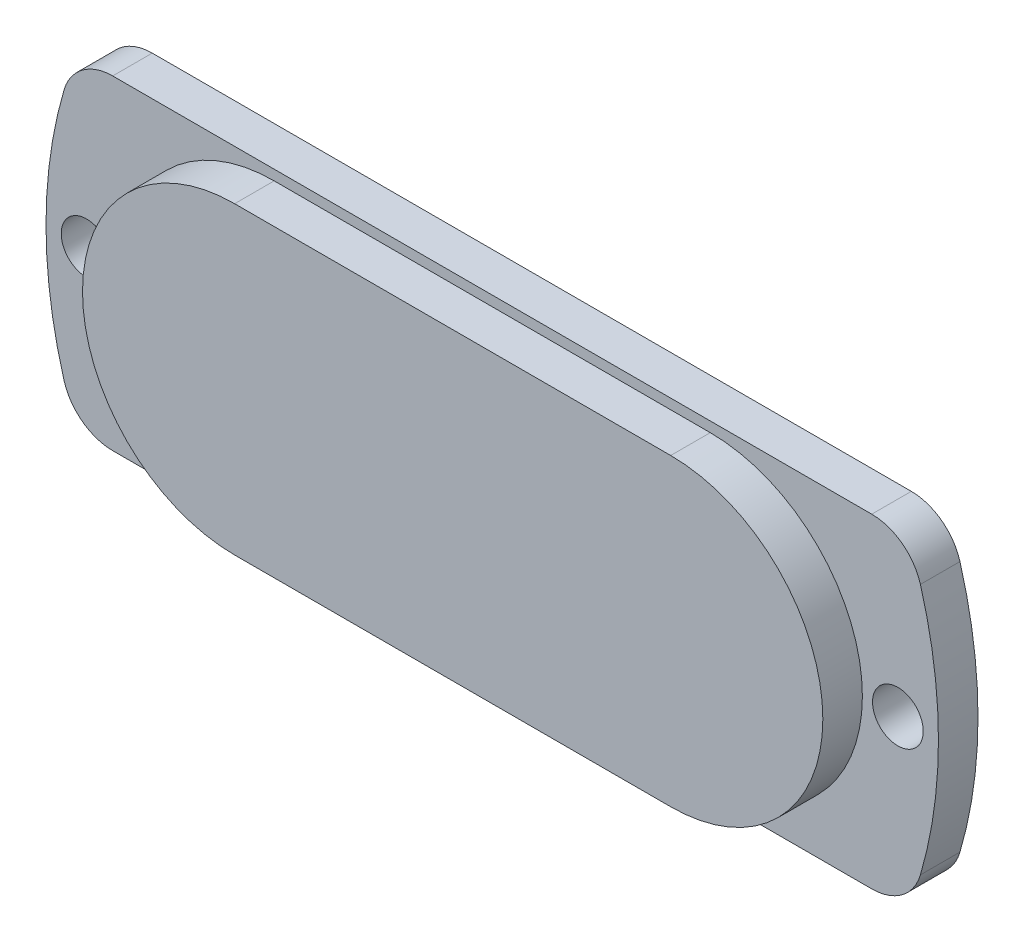
SolidWorks part; units mm, degrees
ref_plane "Front Plane" through (0, 0, 0) normal (0, 0, 1) x (1, 0, 0)
ref_plane "Top Plane" through (0, 0, 0) normal (0, 1, 0) x (1, 0, 0)
ref_plane "Right Plane" through (0, 0, 0) normal (1, 0, 0) x (0, 0, -1)
sketch "Sketch2" plane through (0, 0, 0) normal (0, 0, 1) x (1, 0, 0)
  line L0 (-55.88, 20.32) -> (55.88, 20.32)
  line L10 (-55.88, 20.32) -> (55.88, 20.32)
  line L13 (55.88, -20.32) -> (-55.88, -20.32)
  line L16 (-55.88, 20.32) -> (-55.88, -20.32)
  line L17 (-55.88, -20.32) -> (55.88, -20.32)
  line L18 (55.88, 20.32) -> (55.88, -20.32)
  line L19 (-55.88, 20.32) -> (55.88, -20.32) construction
  line L20 (-55.88, -20.32) -> (55.88, 20.32) construction
  line L21 (0, 20.32) -> (0, -20.32) construction
  circle A12 centre (50.8, 0) radius 3.175
  circle A13 centre (-50.8, 0) radius 3.175
  circle A14 centre (-50.8, 0) radius 3.175
  circle A15 centre (50.8, 0) radius 3.175
  point P3 (0, 0)
  point P4 (50.8, 0)
  point P8 (0, 0)
  dimension "D1" = 101.6
  dimension "D2" = 40.64
  dimension "D3" = 111.76
  dimension "D4" = 6.35
extrude "Boss-Extrude13" add sketch "Sketch2" along normal blind 4.953 contours L18 L0 L16 L13 A12 A13 region at (0, 0, 0)
sketch "Sketch3" plane through (0, 0, 4.953) normal (0, 0, 1) x (1, 0, 0)
  line L0 (27.305, 0) -> (-27.305, 0) construction
  line L1 (27.305, -19.05) -> (-27.305, -19.05)
  line L2 (27.305, 19.05) -> (-27.305, 19.05)
  arc A0 (27.305, -19.05) -> (27.305, 19.05) centre (27.305, 0) ccw
  arc A1 (-27.305, 19.05) -> (-27.305, -19.05) centre (-27.305, 0) ccw
  point P2 (0, 0)
  dimension "D1" = 54.61
  dimension "D2" = 38.1
extrude "Boss-Extrude14" add sketch "Sketch3" along normal blind 4.953 contours L2 A1 L1 A0
sketch "Sketch4" plane through (0, 0, 0) normal (0, 0, -1) x (-1, 0, 0)
  line L0 (55.88, 20.32) -> (-55.88, 20.32) construction
  line L1 (-55.88, -20.32) -> (55.88, -20.32) construction
  line L2 (-55.88, 20.32) -> (-55.88, -20.32) construction
  line L3 (-52.07, 20.32) -> (-55.88, 20.32)
  line L4 (-55.88, 20.32) -> (-55.88, -20.32)
  line L5 (-55.88, -20.32) -> (-52.07, -20.32)
  line L6 (0, 0) -> (0, -20.32) construction
  line L7 (55.88, -20.32) -> (52.07, -20.32)
  line L8 (55.88, 20.32) -> (55.88, -20.32)
  line L9 (52.07, 20.32) -> (55.88, 20.32)
  arc A0 (-52.07, 20.32) -> (-52.07, -20.32) centre (0.2117, 0) ccw
  arc A1 (52.07, 20.32) -> (52.07, -20.32) centre (-0.2117, 0) cw
  line M3 (-55.88, 20.32) -> (-55.88, -20.32)
  line M4 (-55.88, -20.32) -> (55.88, -20.32)
  line M5 (55.88, -20.32) -> (55.88, 20.32)
  line M6 (55.88, 20.32) -> (-55.88, 20.32)
  dimension "D1" = 3.81
extrude "Cut-Extrude1" cut sketch "Sketch4" against normal through all contours A1 L8 M6 | A1 M5 M4 | A0 L4 M4 | A0 M6 M3 region at (54.744, 15.2751, 0) region at (54.744, -15.2751, 0) region at (-54.744, 15.2751, 0) region at (-54.744, -15.2751, 0)
fillet "Fillet1" radius 6.35 4 edges at (-52.07, 20.32, 2.4765) (-52.07, -20.32, 2.4765) (52.07, -20.32, 2.4765) (52.07, 20.32, 2.4765)
